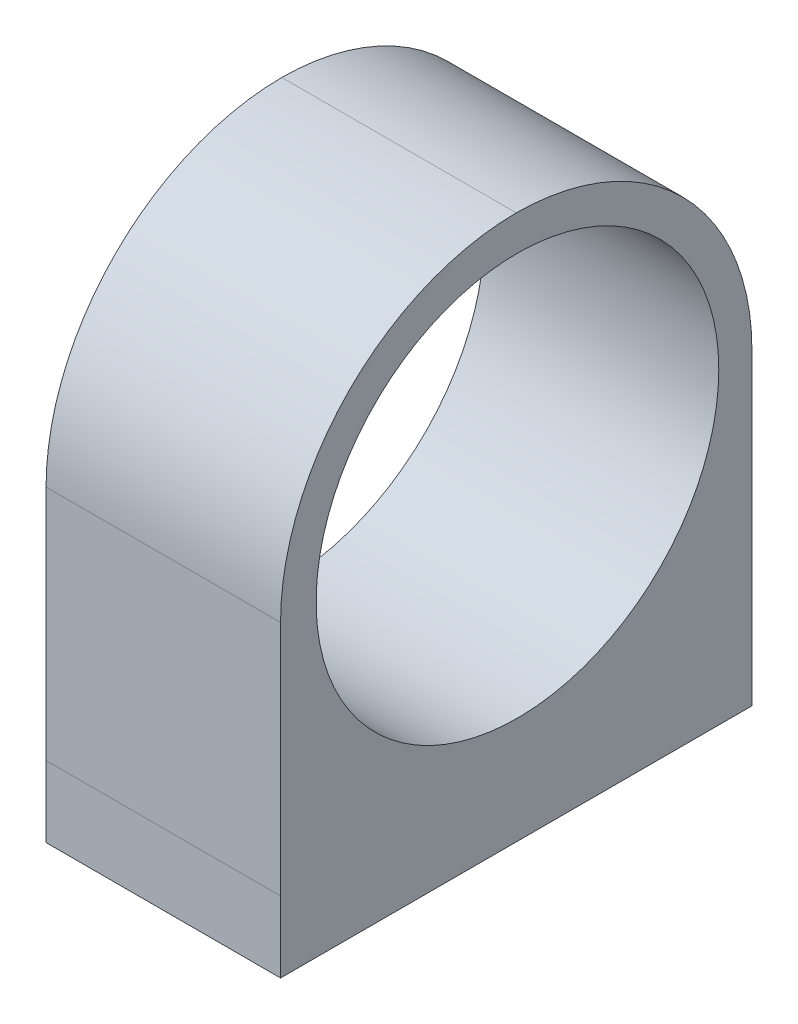
SolidWorks part; units mm, degrees
ref_plane "Front Plane" through (0, 0, 0) normal (0, 0, 1) x (1, 0, 0)
ref_plane "Top Plane" through (0, 0, 0) normal (0, 1, 0) x (1, 0, 0)
ref_plane "Right Plane" through (0, 0, 0) normal (1, 0, 0) x (0, 0, -1)
sketch "Sketch1" plane through (0, 0, 0) normal (0, 1, 0) x (1, 0, 0)
  line L1 (49.5, -99.5) -> (-49.5, -99.5)
  line L2 (49.5, -99.5) -> (49.5, 99.5)
  line L3 (49.5, 99.5) -> (-49.5, 99.5)
  line L4 (-49.5, -99.5) -> (-49.5, 99.5)
  line L5 (49.5, -99.5) -> (-49.5, 99.5) construction
  line L6 (49.5, 99.5) -> (-49.5, -99.5) construction
  point P0 (0, 0)
extrude "Boss-Extrude1" add sketch "Sketch1" along normal blind 30
sketch "Sketch2" plane through (0, 30, 0) normal (0, 1, 0) x (1, 0, 0)
  line L0 (-49.5, 99.5) -> (-49.5, -99.5) construction
  line L1 (49.5, -99.4978) -> (-49.5, -99.4978)
  line L2 (49.5, -99.4978) -> (49.5, 99.4978)
  line L3 (49.5, 99.4978) -> (-49.5, 99.4978)
  line L4 (-49.5, -99.4978) -> (-49.5, 99.4978)
  line L5 (49.5, -99.4978) -> (-49.5, 99.4978) construction
  line L6 (49.5, 99.4978) -> (-49.5, -99.4978) construction
  point P0 (0, 0)
extrude "Boss-Extrude2" add sketch "Sketch2" along normal blind 200
fillet "Fillet1" radius 100 2 edges at (0, 230, -99.4978) (0, 230, 99.4978)
sketch "Sketch3" plane through (49.5, 0, 0) normal (1, 0, 0) x (0, 0, -1)
  circle A0 centre (0.5022, 130) radius 85
extrude "Cut-Extrude1" cut sketch "Sketch3" against normal blind 99
